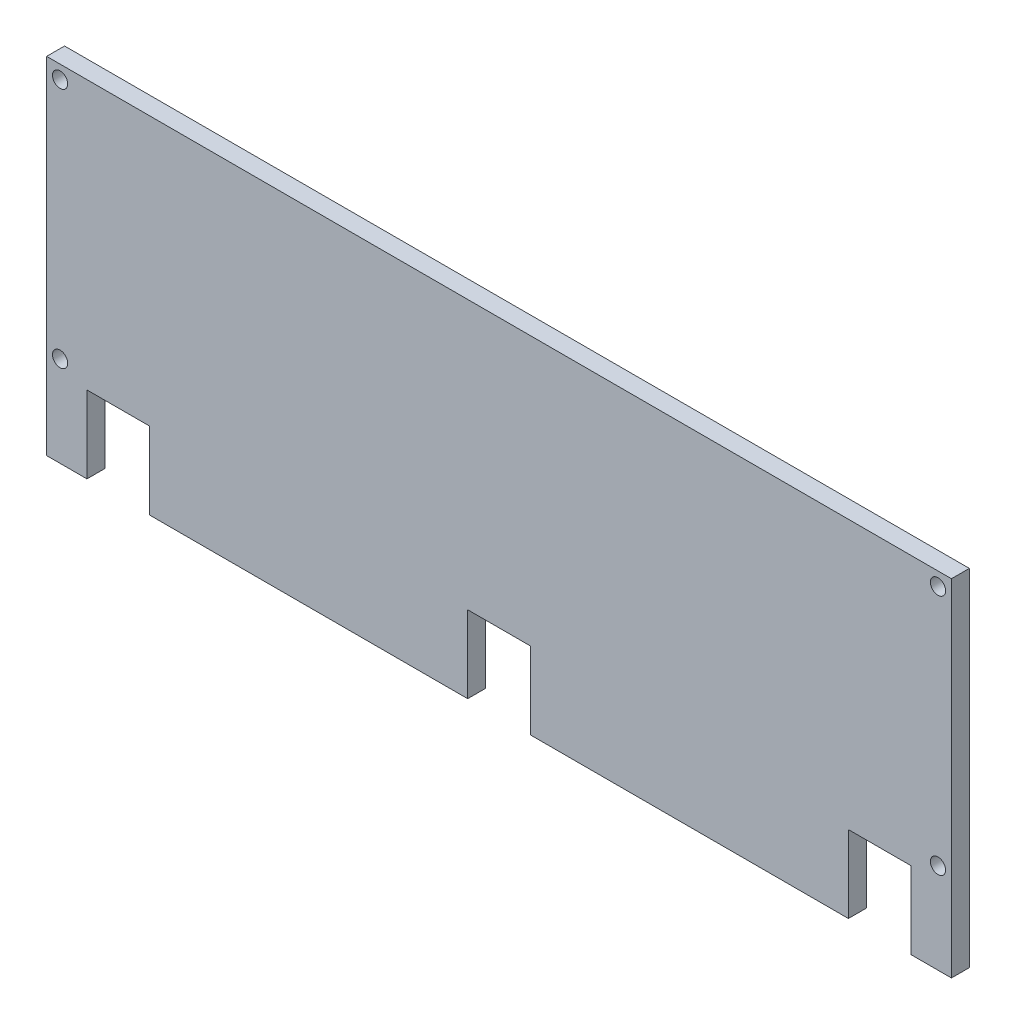
SolidWorks part; units mm, degrees
ref_plane "Front Plane" through (0, 0, 0) normal (0, 0, 1) x (1, 0, 0)
ref_plane "Top Plane" through (0, 0, 0) normal (0, 1, 0) x (1, 0, 0)
ref_plane "Right Plane" through (0, 0, 0) normal (1, 0, 0) x (0, 0, -1)
sketch "Çizim1" plane through (0, 0, 0) normal (0, 0, 1) x (1, 0, 0)
  line L1 (-252.5, 75) -> (252.5, 75)
  line L2 (-252.5, 75) -> (-252.5, -75)
  line L3 (-252.5, -75) -> (252.5, -75)
  line L4 (252.5, 75) -> (252.5, -75)
  line L5 (-252.5, 75) -> (252.5, -75) construction
  line L6 (-252.5, -75) -> (252.5, 75) construction
  point P0 (0, 0)
  dimension "D1" = 150
  dimension "D2" = 505
base flange "Taban-Flanş1" sketch "Çizim1" thickness 10 reverse thickness direction no parameters "D1"=0.7366
sketch "Çizim6" plane through (0, 0, -10) normal (0, 0, -1) x (-1, 0, 0)
  line L1 (252.5, -75) -> (-252.5, -75) construction
  line L2 (252.5, 75) -> (252.5, -75) construction
  circle A0 centre (245, -67.5) radius 4.25
  dimension "D1" = 8.5
  dimension "D2" = 7.5
  dimension "D3" = 7.5
extrude "Kes-Ekstrüzyon1" cut sketch "Çizim6" against normal through all normal cut yes
mirror "Aynalama1" about plane through (0, 0, 0) normal (1, 0, 0) of "Kes-Ekstrüzyon1"
mirror "Aynalama2" about plane through (0, 0, 0) normal (0, 1, 0) of "Aynalama1", "Kes-Ekstrüzyon1"
sketch "Çizim7" plane through (0, 0, 0) normal (0, 0, 1) x (1, 0, 0)
  line L1 (-252.5, -75) -> (-230, -75)
  line L2 (-252.5, -75) -> (-252.5, -118)
  line L3 (-252.5, -118) -> (-230, -118)
  line L4 (-230, -75) -> (-230, -118)
  line L6 (-195, -75) -> (-17.5, -75)
  line L7 (-195, -75) -> (-195, -118)
  line L8 (-195, -118) -> (-17.5, -118)
  line L9 (-17.5, -75) -> (-17.5, -118)
  line L13 (17.5, -75) -> (195, -75)
  line L14 (17.5, -75) -> (17.5, -118)
  line L15 (17.5, -118) -> (195, -118)
  line L16 (195, -75) -> (195, -118)
  line L18 (230, -75) -> (252.5, -75)
  line L19 (230, -75) -> (230, -118)
  line L20 (230, -118) -> (252.5, -118)
  line L21 (252.5, -75) -> (252.5, -118)
  dimension "D1" = 43
  dimension "D2" = 35
  dimension "D3" = 22.5
  dimension "D4" = 177.5
  dimension "D5" = 35
  dimension "D6" = 177.5
  dimension "D7" = 35
  dimension "D8" = 22.5
  dimension "D9" = 43
  dimension "D10" = 75
  dimension "D11" = 75
  dimension "D12" = 75
base flange "Sekme1" sketch "Çizim7" thickness 10 reverse thickness direction no parameters "D1"=0.7366
sketch "Büküm-Çizgileri1" [suppressed] plane through (0, 0, 0) normal (0, 1, 0) x (1, 0, 0)
sketch "Sınırlandırma-Kutusu1" [suppressed] plane through (0, 0, 0) normal (0, 1, 0) x (1, 0, 0)
sheet metal parameters "Sac-Levha1" thickness 10 parameters "D1"=0.7366
flat pattern "Düz-Çoğaltma1" [suppressed]
sketch "Büküm-Çizgileri2" plane through (0, 0, 0) normal (0, 1, 0) x (1, 0, 0)
sketch3d "Sınırlandırma-Kutusu2" [suppressed]
  line L0 (252.5, -75, 0) -> (-252.5, -75, 0) construction
  line L1 (252.5, 75, 0) -> (-252.5, 75, 0) construction
  line L2 (252.5, -75, 0) -> (252.5, 75, 0) construction
  line L3 (-252.5, -75, 0) -> (-252.5, 75, 0) construction
sheet metal parameters "Sac-Levha2" thickness 10 parameters "D1"=0.7366
flat pattern "Düz-Çoğaltma1"
sketch "Büküm-Çizgileri2" plane through (0, 0, 0) normal (0, 1, 0) x (1, 0, 0)
sketch3d "Sınırlandırma-Kutusu2" [suppressed]
  line L0 (-252.5, -75, 0) -> (252.5, -75, 0) construction
  line L1 (-252.5, 75, 0) -> (252.5, 75, 0) construction
  line L2 (-252.5, -75, 0) -> (-252.5, 75, 0) construction
  line L3 (252.5, -75, 0) -> (252.5, 75, 0) construction
sheet metal parameters "Sac-Levha3" thickness 10 parameters "D1"=0.7366
flat pattern "Düz-Çoğaltma1"
sketch "Büküm-Çizgileri2" plane through (0, 0, 0) normal (0, 1, 0) x (1, 0, 0)
sketch3d "Sınırlandırma-Kutusu2" [suppressed]
  line L0 (-252.5, -75, 0) -> (252.5, -75, 0) construction
  line L1 (-252.5, 75, 0) -> (252.5, 75, 0) construction
  line L2 (-252.5, -75, 0) -> (-252.5, 75, 0) construction
  line L3 (252.5, -75, 0) -> (252.5, 75, 0) construction
sheet metal parameters "Sac-Levha4" thickness 10 parameters "D1"=0.7366
flat pattern "Düz-Çoğaltma1"
sketch "Büküm-Çizgileri2" plane through (0, 0, 0) normal (0, 1, 0) x (1, 0, 0)
sketch3d "Sınırlandırma-Kutusu2" [suppressed]
  line L0 (-252.5, -75, 0) -> (252.5, -75, 0) construction
  line L1 (-252.5, 75, 0) -> (252.5, 75, 0) construction
  line L2 (-252.5, -75, 0) -> (-252.5, 75, 0) construction
  line L3 (252.5, -75, 0) -> (252.5, 75, 0) construction
sheet metal parameters "Sac-Levha5" thickness 10 parameters "D1"=0.7366
flat pattern "Düz-Çoğaltma5"
sketch "Büküm-Çizgileri3" plane through (0, 0, 0) normal (0, 1, 0) x (1, 0, 0)
sketch3d "Sınırlandırma-Kutusu3" [suppressed]
  line L0 (-252.5, -118, 0) -> (252.5, -118, 0) construction
  line L1 (-252.5, 75, 0) -> (252.5, 75, 0) construction
  line L2 (-252.5, -118, 0) -> (-252.5, 75, 0) construction
  line L3 (252.5, -118, 0) -> (252.5, 75, 0) construction
